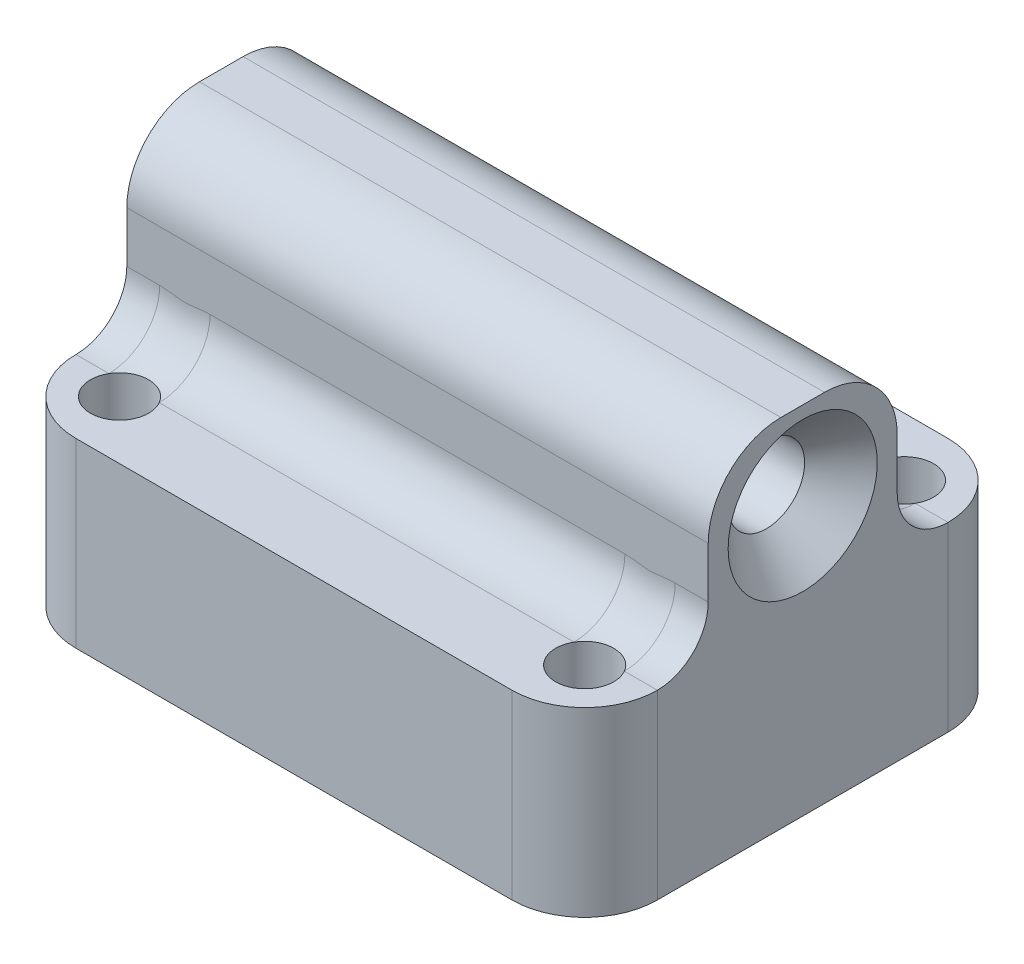
SolidWorks part; units mm, degrees
ref_plane "Front Plane" through (0, 0, 0) normal (0, 0, 1) x (1, 0, 0)
ref_plane "Top Plane" through (0, 0, 0) normal (0, 1, 0) x (1, 0, 0)
ref_plane "Right Plane" through (0, 0, 0) normal (1, 0, 0) x (0, 0, -1)
sketch "Sketch1" plane through (0, 0, 0) normal (0, 1, 0) x (1, 0, 0)
  line L1 (-40, -30) -> (40, -30)
  line L2 (-40, -30) -> (-40, 30)
  line L3 (-40, 30) -> (40, 30)
  line L4 (40, -30) -> (40, 30)
  line L5 (-40, -30) -> (40, 30) construction
  line L6 (-40, 30) -> (40, -30) construction
  point P0 (0, 0)
  dimension "D1" = 80
  dimension "D2" = 60
extrude "Base" add sketch "Sketch1" along normal blind 25
sketch "Sketch3" plane through (0, 25, 0) normal (0, 1, 0) x (1, 0, 0)
  line L0 (40, -30) -> (40, 30) construction
  line L1 (-40, -13) -> (40, -13)
  line L2 (-40, -13) -> (-40, 13)
  line L3 (-40, 13) -> (40, 13)
  line L4 (40, -13) -> (40, 13)
  line L5 (-40, -13) -> (40, 13) construction
  line L6 (-40, 13) -> (40, -13) construction
  point P0 (0, 0)
  dimension "D1" = 26
extrude "Pin block" add sketch "Sketch3" along normal blind 24
sketch "Sketch7" plane through (40, 0, 0) normal (1, 0, 0) x (0, 0, -1)
  line L0 (13, 37) -> (-13, 37) construction
  line L1 (13, 49) -> (13, 25) construction
  line L2 (-13, 49) -> (-13, 25) construction
  circle A0 centre (0, 37) radius 5.2625
  dimension "D1" = 10.525
extrude "Pin hole" cut sketch "Sketch7" against normal through all
sketch "Screw hole placement" plane through (0, 25, 0) normal (0, 1, 0) x (1, 0, 0)
  line L0 (40, -30) -> (40, -13) construction
  line L3 (-40, -30) -> (40, -30) construction
  point P0 (32, -22)
  dimension "D1" = 8
  dimension "D2" = 8
sketch "Sketch8" plane through (0, 25, 0) normal (0, 1, 0) x (1, 0, 0)
  circle A0 centre (32, -22) radius 4
  dimension "D1" = 8
extrude "Cut-Extrude1" cut sketch "Sketch8" against normal offset from surface (15 mm away) 10 up to face at (0, 0, 0)
mirror "Mirror3" about plane through (0, 0, 0) normal (0, 0, 1) of "Cut-Extrude1"
mirror "Mirror4" about plane through (0, 0, 0) normal (1, 0, 0) of "Cut-Extrude1", "Mirror3"
hole_wizard "CSK for #3 Flat Head Machine Screw (100)1" positions "Sketch5" profile "Sketch6" countersink size "#3" standard "ANSI Inch" end condition through all
sketch "Sketch5" plane through (0, 10, 0) normal (0, 1, 0) x (1, 0, 0)
  point P0 (32, -22)
sketch "Sketch6" plane through (32, 10, 22) normal (1, 0, 0) x (0, 0, 1)
  line L0 (0, 0) -> (0, 10)
  line L1 (0, 10) -> (1.397, 10)
  line L2 (1.397, 10) -> (1.397, 0.9484)
  line L3 (1.397, 0.9484) -> (2.5273, 0)
  line L5 (2.5273, 0) -> (0, 0)
  line L6 (-1.397, 0.9484) -> (-2.5273, 0) construction
  line L11 (0, -6.35) -> (0, 107.95) construction
  dimension "Thru Hole Dia." = 2.794
  dimension "Thru Hole Depth" = 10
  dimension "Near C'Sink Dia." = 5.0546
  dimension "Near C'Sink Angle" = 100
mirror "Mirror1" about plane through (0, 0, 0) normal (1, 0, 0) of "CSK for #3 Flat Head Machine Screw (100)1"
mirror "Mirror2" about plane through (0, 0, 0) normal (0, 0, 1) of "CSK for #3 Flat Head Machine Screw (100)1", "Mirror1"
fillet "Fillet2" radius 10 4 edges at (-40, 12.5, -30) (40, 12.5, -30) (40, 12.5, 30) (-40, 12.5, 30)
fillet "Fillet3" radius 10 2 edges at (0, 49, -13) (0, 49, 13)
chamfer "Chamfer1" distance 5 angle 45 1 edges at (40, 37, -5.2625)
fillet "Fillet4" radius 7 2 edges at (0, 25, -13) (0, 25, 13)
